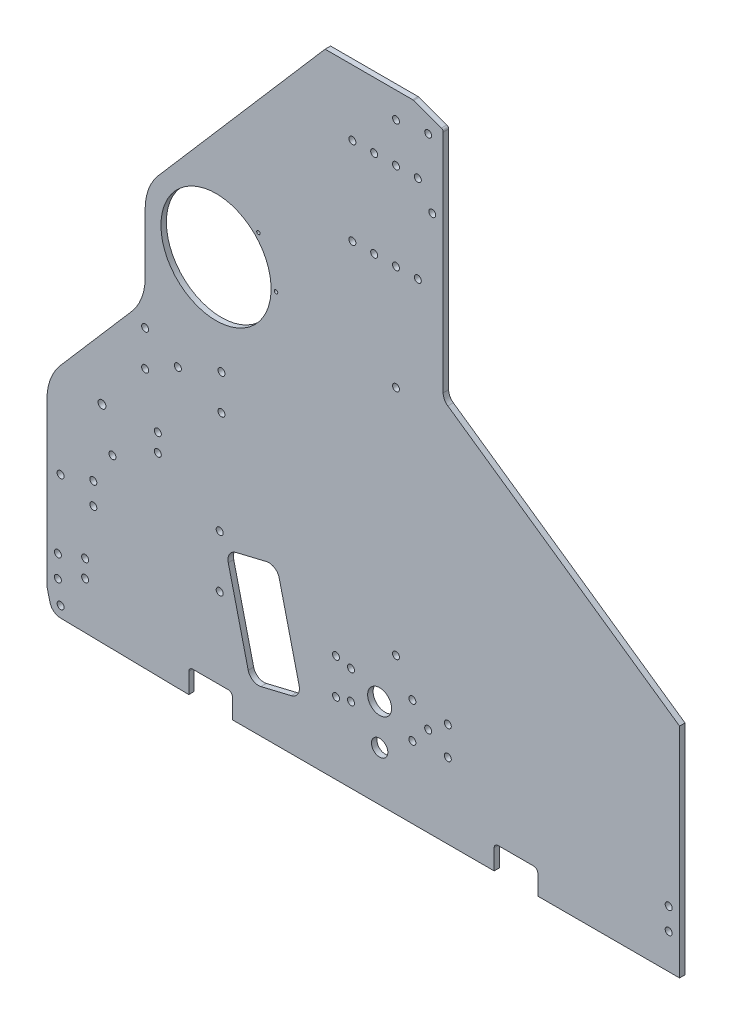
SolidWorks part; units mm, degrees
ref_plane "Front Plane" through (0, 0, 0) normal (0, 0, 1) x (1, 0, 0)
ref_plane "Top Plane" through (0, 0, 0) normal (0, 1, 0) x (1, 0, 0)
ref_plane "Right Plane" through (0, 0, 0) normal (1, 0, 0) x (0, 0, -1)
sketch "Sketch1" plane through (0, 0, 0) normal (0, 0, 1) x (1, 0, 0)
  line L0 (82.55, -20.32) -> (82.55, -6.35)
  line L2 (0, 0) -> (0, 157.48)
  line L4 (368.3, -20.32) -> (368.3, 106.68)
  line L5 (82.55, -6.35) -> (107.95, -6.35)
  line L6 (107.95, -6.35) -> (107.95, -20.32)
  line L7 (107.95, -20.32) -> (260.35, -20.32)
  line L8 (260.35, -20.32) -> (260.35, -6.35)
  line L9 (260.35, -6.35) -> (285.75, -6.35)
  line L10 (285.75, -6.35) -> (285.75, -20.32)
  line L11 (285.75, -20.32) -> (368.3, -20.32)
  line L12 (361.95, 12.7) -> (368.3, 12.7) construction
  line L13 (0, 0) -> (6.35, 0) construction
  line L14 (0.1896, -7.8901) -> (1.7771, -14.2401)
  line L15 (7.8295, -19.0491) -> (82.55, -20.32)
  line L16 (0, 0) -> (0, -6.35)
  line L17 (76.2, 141.605) -> (79.375, 141.605) construction
  line L18 (57.15, 131.2863) -> (101.6, 131.2862) construction
  line L19 (57.15, 131.2863) -> (57.15, 151.9238) construction
  line L20 (101.6, 131.2862) -> (101.6, 151.9237) construction
  line L21 (57.15, 151.9238) -> (101.6, 151.9237) construction
  line L22 (57.15, 131.2863) -> (101.6, 151.9237) construction
  line L23 (101.6, 131.2862) -> (57.15, 151.9238) construction
  line L25 (203.2, 59.805) -> (203.2, 194.805) construction
  line L26 (203.2, 194.805) -> (203.2, 329.805) construction
  line L27 (355.6, 332.105) -> (330.2, 332.105) construction
  line L28 (330.2, 332.105) -> (330.2, 217.805) construction
  line L29 (330.2, 217.805) -> (355.6, 217.805) construction
  line L30 (355.6, 217.805) -> (355.6, 332.105) construction
  line L31 (203.2, 344.805) -> (203.2, 194.805) construction
  line L32 (50.8, 332.105) -> (76.2, 332.105) construction
  line L33 (76.2, 332.105) -> (76.2, 217.805) construction
  line L34 (50.8, 217.805) -> (50.8, 332.105) construction
  line L35 (76.2, 217.805) -> (50.8, 217.805) construction
  line L36 (213.2, 344.805) -> (230.6638, 338.455)
  line L37 (203.2, 344.805) -> (161.925, 344.805)
  line L38 (203.2, 344.805) -> (213.2, 344.805)
  line L39 (348.5362, 344.805) -> (413.4623, 344.805)
  line L40 (348.5362, 344.805) -> (230.6638, 344.805) construction
  line L42 (161.925, 344.805) -> (0, 157.48)
  line L44 (230.6638, 338.455) -> (230.6638, 202.565)
  line L45 (230.6638, 202.565) -> (368.3, 106.68)
  line L46 (213.2, 344.805) -> (-141.0713, 344.805) construction
  circle A0 centre (6.35, 0) radius 2.032
  circle A1 centre (6.35, 12.7) radius 2.032
  circle A2 centre (361.95, 0) radius 2.032
  circle A3 centre (361.95, 12.7) radius 2.032
  arc A5 (1.7771, -14.2401) -> (7.8295, -19.0491) centre (7.9375, -12.7) ccw
  circle A6 centre (7.9375, -12.7) radius 2.032
  arc A7 (0, -6.35) -> (0.1896, -7.8901) centre (6.35, -6.35) ccw
  circle A8 centre (38.1, 78.105) radius 2.032
  circle A9 centre (76.2, 141.605) radius 2.032
  circle A10 centre (101.6, 131.2862) radius 2.032
  circle A11 centre (101.6, 151.9237) radius 2.032
  circle A12 centre (57.15, 151.9238) radius 2.032
  circle A13 centre (57.15, 131.2863) radius 2.032
  circle A15 centre (203.2, 59.805) radius 2
  circle A16 centre (203.2, 194.805) radius 2
  circle A17 centre (203.2, 329.805) radius 2
  circle A18 centre (63.5, 313.055) radius 2.032
  circle A20 centre (355.6, 332.105) radius 2.032
  circle A21 centre (330.2, 332.105) radius 2.032
  circle A22 centre (355.6, 217.805) radius 2.032
  circle A23 centre (330.2, 217.805) radius 2.032
  circle A24 centre (50.8, 332.105) radius 2.032
  circle A25 centre (76.2, 332.105) radius 2.032
  circle A26 centre (50.8, 217.805) radius 2.032
  circle A27 centre (76.2, 217.805) radius 2.032
  circle A28 centre (221.9319, 332.105) radius 2
  circle A29 centre (224.3138, 293.243) radius 2.032
  point P82 (203.2, 344.805)
  point P83 (221.9319, 341.63)
  dimension "D6" = 4.064
  dimension "D10" = 6.35
  dimension "D11" = 4.064
  dimension "D17" = 38.1
  dimension "D27" = 4
  dimension "D31" = 4.064
  dimension "D32" = 41.275
  dimension "D36" = 4.064
  dimension "D47" = 45.212
  dimension "D48" = 4.064
  dimension "D2" = 127
  dimension "D3" = 13.97
  dimension "D4" = 25.4
  dimension "D5" = 152.4
  dimension "D7" = 12.7
  dimension "D8" = 6.35
  dimension "D9" = 20.32
  dimension "D12" = 12.7
  dimension "D13" = 1.5875
  dimension "D14" = 82.55
  dimension "D15" = 368.3
  dimension "D16" = 6.35
  dimension "D18" = 98.425
  dimension "D19" = 38.1
  dimension "D20" = 63.5
  dimension "D21" = 3.175
  dimension "D22" = 270
  dimension "D23" = 20.6375
  dimension "D24" = 44.45
  dimension "D28" = 135
  dimension "D29" = 12.7
  dimension "D30" = 15
  dimension "D33" = 63.5
  dimension "D34" = 27.4638
  dimension "D37" = 114.3
  dimension "D38" = 25.4
  dimension "D39" = 12.7
  dimension "D40" = 157.48
  dimension "D41" = 142.24
  dimension "D42" = 365.125
  dimension "D43" = 10
  dimension "D44" = 6.35
  dimension "D45" = 31.75
  dimension "D46" = 6.35
  dimension "D49" = 6.35
  dimension "D50" = 203.2
extrude "Boss-Extrude1" add sketch "Sketch1" along normal blind 3.175 contours L16 A7 L14 A5 L15 L2 A0 A1 A6 region at (171.3968, 119.6345, 0)
fillet "Fillet1" radius 2.286 4 edges at (285.75, -6.35, 1.5875) (107.95, -6.35, 1.5875) (260.35, -6.35, 1.5875) (82.55, -6.35, 1.5875)
fillet "Fillet2" radius 6.35 1 edges at (230.6638, 202.565, 1.5875)
sketch "Sketch2" plane through (0, 0, 0) normal (0, 0, -1) x (-1, 0, 0)
  circle A0 centre (-100.5528, 71.086) radius 2.032 construction
  circle A1 centre (-100.5528, 40.606) radius 2.032 construction
  circle A2 centre (-22.225, 18.2025) radius 2.032 construction
  circle A3 centre (-22.225, 8.0425) radius 2.032 construction
  circle A4 centre (-100.5528, 71.086) radius 2.032
  circle A5 centre (-100.5528, 40.606) radius 2.032
  circle A6 centre (-22.225, 18.2025) radius 2.032
  circle A7 centre (-22.225, 8.0425) radius 2.032
extrude "Cut-Extrude1" cut sketch "Sketch2" against normal through all
fillet "Fillet3" radius 1.5875 2 edges at (230.6638, 338.455, 1.5875) (213.2, 344.805, 1.5875)
sketch "Sketch3" plane through (0, 0, 3.175) normal (0, 0, 1) x (1, 0, 0)
  line L0 (132.9524, 63.2646) -> (132.7215, 64.2281) construction
  line L1 (128.3814, 66.8897) -> (110.6828, 62.6472) construction
  line L2 (114.5132, 58.4237) -> (126.8822, 61.3887) construction
  line L3 (108.0212, 58.3071) -> (108.2522, 57.3436) construction
  line L4 (131.2006, 57.703) -> (140.0164, 20.9265) construction
  line L5 (144.0993, 16.7636) -> (132.9524, 63.2646) construction
  line L6 (108.2522, 57.3436) -> (119.3991, 10.8426) construction
  line L7 (121.1509, 16.4042) -> (112.3351, 53.1807) construction
  line L8 (119.3991, 10.8426) -> (119.6301, 9.8791) construction
  line L9 (144.3303, 15.8001) -> (144.0993, 16.7636) construction
  line L10 (137.8383, 15.6835) -> (125.4694, 12.7185) construction
  line L11 (123.9701, 7.2175) -> (141.6687, 11.4601) construction
  line L12 (132.9524, 63.2646) -> (132.7215, 64.2281)
  line L13 (128.3814, 66.8897) -> (110.6828, 62.6472)
  line L14 (114.5132, 58.4237) -> (126.8822, 61.3887)
  line L15 (108.0212, 58.3071) -> (108.2522, 57.3436)
  line L16 (131.2006, 57.703) -> (140.0164, 20.9265)
  line L17 (144.0993, 16.7636) -> (132.9524, 63.2646)
  line L18 (108.2522, 57.3436) -> (119.3991, 10.8426)
  line L19 (121.1509, 16.4042) -> (112.3351, 53.1807)
  line L20 (119.3991, 10.8426) -> (119.6301, 9.8791)
  line L21 (144.3303, 15.8001) -> (144.0993, 16.7636)
  line L22 (137.8383, 15.6835) -> (125.4694, 12.7185)
  line L23 (123.9701, 7.2175) -> (141.6687, 11.4601)
  line L24 (127.7894, 69.3598) -> (110.0908, 65.1172)
  line L25 (105.5512, 57.715) -> (105.7822, 56.7515)
  line L26 (105.7822, 56.7515) -> (116.9291, 10.2505)
  line L27 (116.9291, 10.2505) -> (117.16, 9.287)
  line L28 (124.5622, 4.7475) -> (142.2608, 8.99)
  line L29 (146.8003, 16.3922) -> (146.5694, 17.3557)
  line L30 (146.5694, 17.3557) -> (135.4225, 63.8567)
  line L31 (135.4225, 63.8567) -> (135.1915, 64.8202)
  line L32 (14.605, -0.1369) -> (103.7278, 32.3011) construction
  line L33 (14.605, -0.1369) -> (103.7278, 32.3011)
  line L35 (-39.6666, 74.7152) -> (103.7278, 126.9065) construction
  arc A0 (132.7215, 64.2281) -> (128.6308, 66.9403) centre (129.2206, 63.3889) ccw construction
  arc A1 (110.6828, 62.6472) -> (110.4377, 62.5791) centre (111.522, 59.1463) ccw construction
  arc A2 (128.6308, 66.9403) -> (128.3814, 66.8897) centre (129.2206, 63.3889) ccw construction
  arc A3 (110.4377, 62.5791) -> (108.0212, 58.3071) centre (111.522, 59.1463) ccw construction
  arc A4 (119.6301, 9.8791) -> (123.7207, 7.1669) centre (123.1309, 10.7183) ccw construction
  arc A5 (141.9139, 11.5281) -> (144.3303, 15.8001) centre (140.8295, 14.9609) ccw construction
  arc A6 (141.6687, 11.4601) -> (141.9139, 11.5281) centre (140.8295, 14.9609) ccw construction
  arc A7 (123.7207, 7.1669) -> (123.9701, 7.2175) centre (123.1309, 10.7183) ccw construction
  arc A8 (132.7215, 64.2281) -> (128.6308, 66.9403) centre (129.2206, 63.3889) ccw
  arc A9 (110.6828, 62.6472) -> (110.4377, 62.5791) centre (111.522, 59.1463) ccw
  arc A10 (128.6308, 66.9403) -> (128.3814, 66.8897) centre (129.2206, 63.3889) ccw
  arc A11 (110.4377, 62.5791) -> (108.0212, 58.3071) centre (111.522, 59.1463) ccw
  arc A12 (119.6301, 9.8791) -> (123.7207, 7.1669) centre (123.1309, 10.7183) ccw
  arc A13 (141.9139, 11.5281) -> (144.3303, 15.8001) centre (140.8295, 14.9609) ccw
  arc A14 (141.6687, 11.4601) -> (141.9139, 11.5281) centre (140.8295, 14.9609) ccw
  arc A15 (123.7207, 7.1669) -> (123.9701, 7.2175) centre (123.1309, 10.7183) ccw
  arc A16 (110.0908, 65.1172) -> (109.6726, 65.0012) centre (111.522, 59.1463) ccw
  arc A17 (109.6726, 65.0012) -> (105.5512, 57.715) centre (111.522, 59.1463) ccw
  arc A18 (117.16, 9.287) -> (124.1369, 4.6613) centre (123.1309, 10.7183) ccw
  arc A19 (124.1369, 4.6613) -> (124.5622, 4.7475) centre (123.1309, 10.7183) ccw
  arc A20 (142.2608, 8.99) -> (142.6789, 9.1061) centre (140.8295, 14.9609) ccw
  arc A21 (142.6789, 9.1061) -> (146.8003, 16.3922) centre (140.8295, 14.9609) ccw
  arc A22 (135.1915, 64.8202) -> (128.2147, 69.446) centre (129.2206, 63.3889) ccw
  arc A23 (128.2147, 69.446) -> (127.7894, 69.3598) centre (129.2206, 63.3889) ccw
  circle A24 centre (64.5259, 102.9405) radius 2.032 construction
  circle A25 centre (64.5259, 92.5258) radius 2.032 construction
  circle A26 centre (133.35, 208.2281) radius 1.016 construction
  circle A30 centre (26.9875, 46.9531) radius 2.032 construction
  circle A31 centre (26.9875, 59.6531) radius 2.032 construction
  circle A32 centre (7.9375, 53.3031) radius 2.032 construction
  circle A33 centre (26.9875, 46.9531) radius 2.032
  circle A34 centre (26.9875, 59.6531) radius 2.032
  circle A35 centre (7.9375, 53.3031) radius 2.032
  circle A37 centre (32.0306, 100.8109) radius 31.75 construction
  circle A38 centre (32.0306, 100.8109) radius 2.286
  circle A39 centre (123.1207, 232.9238) radius 1.016 construction
  circle A40 centre (64.5259, 102.9405) radius 2.032
  circle A41 centre (64.5259, 92.5258) radius 2.032
  circle A42 centre (133.35, 208.2281) radius 1.016
  circle A43 centre (123.1207, 232.9238) radius 1.016
  ellipse E0 centre (124.5974, 48.8487) end of major axis (128.5376, 61.3578) minor radius 6 (131.2006, 57.703) -> (126.8822, 61.3887) ccw construction
  ellipse E1 centre (122.2349, 48.2824) end of major axis (113.0518, 57.6456) minor radius 6 (114.5132, 58.4237) -> (112.3351, 53.1807) ccw construction
  ellipse E2 centre (127.7541, 25.2585) end of major axis (131.6942, 37.7675) minor radius 6 (121.1509, 16.4042) -> (125.4694, 12.7185) ccw construction
  ellipse E3 centre (130.1166, 25.8248) end of major axis (139.2998, 16.4616) minor radius 6 (137.8383, 15.6835) -> (140.0164, 20.9265) ccw construction
  ellipse E4 centre (124.5974, 48.8487) end of major axis (120.6573, 36.3397) minor radius 6 (131.2006, 57.703) -> (126.8822, 61.3887) ccw
  ellipse E5 centre (122.2349, 48.2824) end of major axis (131.4181, 38.9192) minor radius 6 (114.5132, 58.4237) -> (112.3351, 53.1807) ccw
  ellipse E6 centre (127.7541, 25.2585) end of major axis (131.6942, 37.7675) minor radius 6 (121.1509, 16.4042) -> (125.4694, 12.7185) ccw
  ellipse E7 centre (130.1166, 25.8248) end of major axis (139.2998, 16.4616) minor radius 6 (137.8383, 15.6835) -> (140.0164, 20.9265) ccw
  point P115 (32.0306, 100.8109)
  dimension "D3" = 63.5
  dimension "D4" = 4.572
  dimension "D2" = 88.9
  dimension "D1" = 2.54
extrude "Cut-Extrude2" cut sketch "Sketch3" against normal through all contours A22 A23 L24 A16 A17 L25 L26 L27 A18 A19 L28 A20 A21 L29 L30 L31 A15 A12 L20 L18 L15 A11 A9 L13 A10 A8 L12 L17 L21 A13 A14 L23 | A12 A15 L23 A14 A13 L21 L17 L12 A8 A10 L13 A9 A11 L15 L18 L20 E7 L22 E6 L19 E5 L14 E4 L16 | L22 E7 L16 E4 L14 E5 L19 E6 | A38 | A41 | A40 | A35 | A34 | A33 | A43 | A42 region at (137.844, 39.8506, 3.175) region at (126.1758, 37.0536, 3.175) region at (128.1544, 68.6507, 3.175) region at (32.0306, 100.8109, 3.175) region at (64.5259, 102.9405, 3.175) region at (64.5259, 92.5258, 3.175)
sketch "Sketch4" plane through (0, 0, 3.175) normal (0, 0, 1) x (1, 0, 0)
  line L0 (57.15, 151.9238) -> (101.6, 151.9237) construction
  line L1 (168.275, 21.4312) -> (212.725, 21.4312) construction
  line L2 (168.275, 21.4312) -> (168.275, 42.0687) construction
  line L3 (168.275, 42.0687) -> (212.725, 42.0687) construction
  line L4 (212.725, 21.4312) -> (212.725, 42.0687) construction
  line L5 (168.275, 21.4312) -> (212.725, 42.0687) construction
  line L6 (168.275, 42.0687) -> (212.725, 21.4312) construction
  line L7 (57.15, 131.2863) -> (57.15, 151.9238) construction
  line L8 (107.95, -20.32) -> (260.35, -20.32) construction
  line L9 (193.675, 31.75) -> (177.005, 31.75) construction
  line L10 (190.5, 31.75) -> (193.675, 31.75) construction
  line L11 (6.35, 12.7) -> (361.95, 12.7) construction
  line L12 (107.95, -6.35) -> (107.95, -20.32) construction
  line L13 (193.675, 31.75) -> (220.6625, 31.75) construction
  line L14 (177.005, 23.4569) -> (177.005, 40.0431) construction
  line L15 (213.2, 44.805) -> (193.2, 44.805) construction
  line L16 (213.2, 44.805) -> (213.2, 344.805) construction
  line L17 (213.2, 344.805) -> (193.2, 344.805) construction
  line L18 (193.2, 44.805) -> (193.2, 344.805) construction
  line L19 (213.2, 44.805) -> (193.2, 344.805) construction
  line L20 (213.2, 344.805) -> (193.2, 44.805) construction
  line L21 (226.9319, 332.105) -> (226.9319, 31.75) construction
  line L22 (237.33, 40.0431) -> (233.3612, 40.0431) construction
  line L23 (237.33, 23.4569) -> (233.3612, 23.4569) construction
  circle A0 centre (168.275, 42.0687) radius 2.032
  circle A1 centre (212.725, 42.0687) radius 2.032
  circle A2 centre (212.725, 21.4312) radius 2.032
  circle A3 centre (168.275, 21.4312) radius 2.032
  circle A4 centre (193.675, 31.75) radius 6.985
  circle A7 centre (220.6625, 31.75) radius 14.2875 construction
  circle A8 centre (193.675, 31.75) radius 12.7 construction
  circle A9 centre (177.005, 40.0431) radius 2.032
  circle A10 centre (177.005, 23.4569) radius 2.032
  circle A11 centre (237.33, 40.0431) radius 2.032 construction
  circle A12 centre (237.33, 23.4569) radius 2.032 construction
  circle A13 centre (193.675, 8.4667) radius 4.7625
  circle A14 centre (221.9319, 31.75) radius 2.032
  circle A15 centre (221.9319, 31.75) radius 5 construction
  circle A16 centre (221.9319, 332.105) radius 5 construction
  circle A17 centre (233.3612, 23.4569) radius 2.032
  circle A18 centre (233.3612, 40.0431) radius 2.032
  point P0 (190.5, 31.75)
  point P26 (203.2, 194.805)
  point P38 (177.005, 31.75)
  dimension "D1" = 4.064
  dimension "D4" = 13.97
  dimension "D7" = 9.525
  dimension "D10" = 25.4
  dimension "D11" = 28.575
  dimension "D16" = 10
  dimension "D17" = 4.064
  dimension "D18" = 10
  dimension "D2" = 52.07
  dimension "D3" = 3.175
  dimension "D5" = 82.55
  dimension "D6" = 26.9875
  dimension "D8" = 20
  dimension "D9" = 300
  dimension "D12" = 16.67
  dimension "D13" = 16.5862
  dimension "D14" = 60.325
  dimension "D15" = 23.2833
  dimension "D19" = 3.9688
extrude "Cut-Extrude3" cut sketch "Sketch4" against normal through all
sketch "Sketch5" plane through (0, 0, -187.325) normal (0, 0, -1) x (-1, 0, 0)
  line L0 (-57.15, 223.5947) -> (-57.15, 165.3337)
  line L1 (-161.925, 344.805) -> (-52.7201, 218.4699) construction
  line L2 (-57.15, 165.3337) -> (0, 99.219)
  line L3 (0, -6.35) -> (0, 157.48) construction
  line L4 (-50.4199, 215.8089) -> (0, 157.48) construction
  line L5 (-50.4199, 215.8089) -> (0, 157.48) construction
  line L6 (-57.15, 223.5947) -> (0, 157.48)
  line L7 (0, 157.48) -> (0, 99.219)
  circle A0 centre (-98.425, 208.2281) radius 32.0675
  dimension "D3" = 64.135
  dimension "D1" = 38.1
  dimension "D2" = 57.15
  dimension "D4" = 41.275
  dimension "D5" = 41.275
extrude "Cut-Extrude5" cut sketch "Sketch5" against normal through all contours A0 | L7 L6 L0 L2 region at (28.575, 161.4068, -187.325) region at (98.425, 208.2281, -187.325)
fillet "Fillet4" radius 31.75 3 edges at (0, 99.219, 1.5875) (57.15, 165.3337, 1.5875) (57.15, 223.5947, 1.5875)
sketch "Sketch7" plane through (0, 0, 0) normal (0, 0, -1) x (-1, 0, 0)
  circle A0 centre (-215.9, 306.705) radius 2.032 construction
  arc A1 (-201.2648, 307.3246) -> (-201.2648, 306.0854) centre (-203.2, 306.705) ccw construction
  arc A2 (-176.9699, 308.5597) -> (-176.9699, 304.8503) centre (-177.8, 306.705) ccw construction
  arc A3 (-192.4352, 306.0854) -> (-192.4352, 307.3246) centre (-190.5, 306.705) ccw construction
  circle A4 centre (-215.9, 255.905) radius 2.032 construction
  arc A5 (-201.2648, 256.5246) -> (-201.2648, 255.2854) centre (-203.2, 255.905) ccw construction
  arc A6 (-192.4352, 255.2854) -> (-192.4352, 256.5246) centre (-190.5, 255.905) ccw construction
  arc A7 (-176.9699, 257.7597) -> (-176.9699, 254.0503) centre (-177.8, 255.905) ccw construction
  circle A8 centre (-215.9, 306.705) radius 2.032
  arc A9 (-201.2648, 307.3246) -> (-201.2648, 306.0854) centre (-203.2, 306.705) ccw
  arc A10 (-176.9699, 308.5597) -> (-176.9699, 304.8503) centre (-177.8, 306.705) ccw
  arc A11 (-192.4352, 306.0854) -> (-192.4352, 307.3246) centre (-190.5, 306.705) ccw
  circle A12 centre (-215.9, 255.905) radius 2.032
  arc A13 (-201.2648, 256.5246) -> (-201.2648, 255.2854) centre (-203.2, 255.905) ccw
  arc A14 (-192.4352, 255.2854) -> (-192.4352, 256.5246) centre (-190.5, 255.905) ccw
  arc A15 (-176.9699, 257.7597) -> (-176.9699, 254.0503) centre (-177.8, 255.905) ccw
  circle A16 centre (-203.2, 255.905) radius 2.032
  circle A17 centre (-190.5, 255.905) radius 2.032
  circle A18 centre (-203.2, 306.705) radius 2.032
  circle A19 centre (-190.5, 306.705) radius 2.032
  circle A20 centre (-177.8, 306.705) radius 2.032
  circle A21 centre (-177.8, 255.905) radius 2.032
  dimension "D1" = 4.064
extrude "Cut-Extrude6" cut sketch "Sketch7" against normal through all contours A12 | A13 A16 | A14 A17 | A15 A21 | A8 | A9 A18 | A11 A19 | A10 A20 region at (215.9, 306.705, 0) region at (203.2, 306.705, 0) region at (177.8, 306.705, 0) region at (190.5, 306.705, 0) region at (215.9, 255.905, 0) region at (203.2, 255.905, 0) region at (190.5, 255.905, 0) region at (177.8, 255.905, 0)
